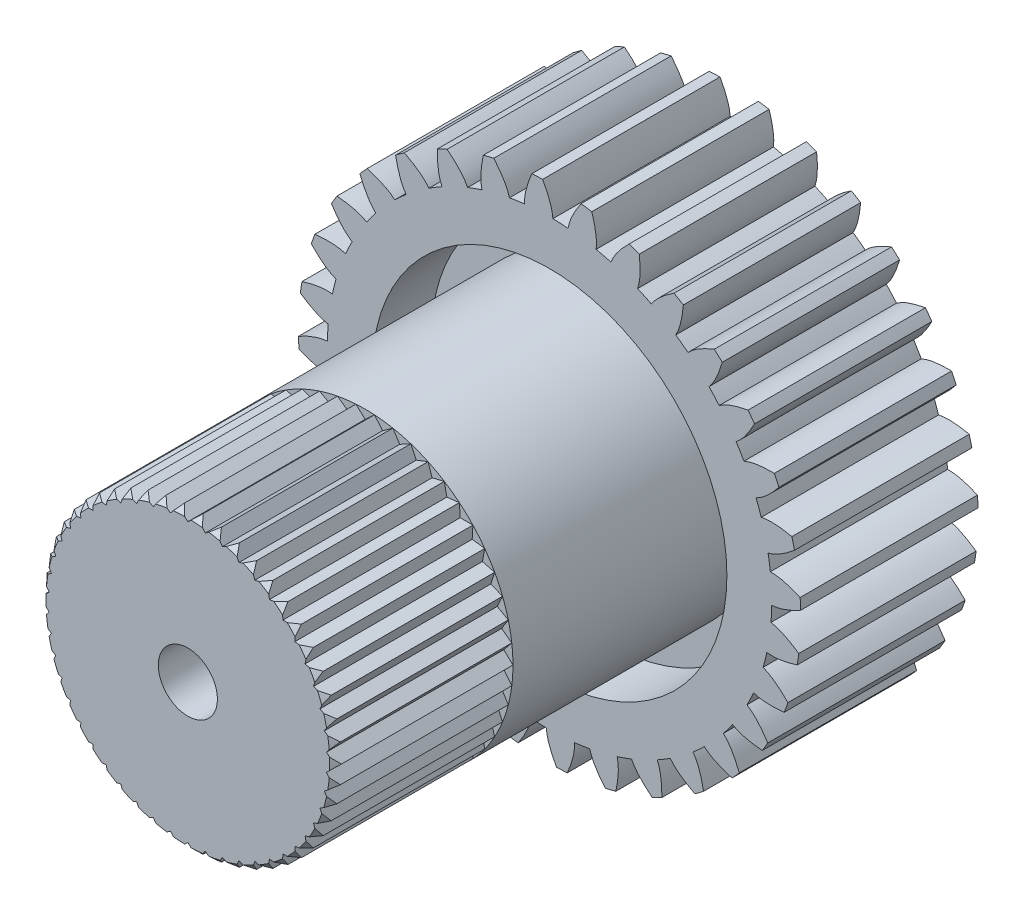
SolidWorks part; units mm, degrees
ref_plane "Front Plane" through (0, 0, 0) normal (0, 0, 1) x (1, 0, 0)
ref_plane "Top Plane" through (0, 0, 0) normal (0, 1, 0) x (1, 0, 0)
ref_plane "Right Plane" through (0, 0, 0) normal (1, 0, 0) x (0, 0, -1)
sketch "punti involuta" plane through (0, 0, 0) normal (0, 0, 1) x (1, 0, 0)
  line L0 (0, 0) -> (0, 4.6277) construction
  line L1 (-3.4916, 4) -> (3.4916, 4) construction
  line L2 (-3.4916, 2.7292) -> (3.4916, 5.2708) construction
  line L3 (0, 0) -> (-1.2856, 3.5321) construction
  line L4 (-1.2856, 3.5321) -> (0, 4) construction
  line L5 (-1.9173, 3.233) -> (-0.1385, 4.2879) construction
  line L6 (-0.9999, 3.6233) -> (0.0297, 3.9075) construction
  circle A0 centre (0, 0) radius 4 construction
  circle A1 centre (0, 0) radius 3.7588 construction
  arc A2 (-1.2856, 3.5321) -> (-1.9173, 3.233) centre (0, 0) ccw construction
  arc A3 (-1.2856, 3.5321) -> (-0.9999, 3.6233) centre (0, 0) cw construction
  arc A4 (-1.2856, 3.5321) -> (0.056, 3.7584) centre (0, 0) cw construction
  point P4 (0, 4)
  point P7 (0, 4)
  dimension "D1" = 8
  dimension "D2" = 20
  dimension "D3" = 1.3681
  dimension "D5" = 2.0681
  dimension "D7" = 1.0681
  dimension "D4" = 0.7
  dimension "D6" = 0.3
  dimension "D8" = 1.3681
sketch "diametro testa" plane through (0, 0, 0) normal (0, 0, 1) x (1, 0, 0)
  circle A0 centre (0, 0) radius 4.25
  dimension "D1" = 8.5
sketch "profilo" plane through (0, 0, 0) normal (0, 0, 1) x (1, 0, 0)
  line L0 (0, 0) -> (-0.1844, 3.7542) construction
  line L1 (0, 0) -> (0, 4.6277) construction
  line L2 (-0.1844, 3.7542) -> (-0.2085, 4.2449)
  arc A1 (-0.2085, 4.2449) -> (-0.1168, 4.2484) centre (0, 0) cw
  circle A3 centre (0, 0) radius 4.25 construction
  arc A4 (0.056, 3.7584) -> (-0.1844, 3.7542) centre (0, 0) ccw
  arc A5 (0.056, 3.7584) -> (-1.2856, 3.5321) centre (0, 0) ccw construction
  circle A6 centre (0, 0) radius 3.7588 construction
  spline S0 degree 3 poles (-0.1385, 4.2879) (-0.0478, 4.1243) (0.0412, 3.9487) (0.056, 3.7584) knots 0 0 0 0 1 1 1 1
  dimension "D1" = 2.813
sketch "diametro base" plane through (0, 0, 0) normal (0, 0, 1) x (1, 0, 0)
  circle A0 centre (0, 0) radius 3.7588
extrude "Boss-Extrude7" add sketch "profilo" along normal blind 3 contours S0 A1 L2 A4 region at (-0.0968, 3.9689, 0)
ref_plane "Plane1" through (0, 0, 0) normal (0.9988, 0.0491, 0) x (-0.0491, 0.9988, 0)
mirror "Mirror1" about plane through (0, 0, 0) normal (0.9988, 0.0491, 0) of bodies 112
pattern_circular "CirPattern1" count 32 over 360 about axis through (0, 0, 3) along (0, 0, 1) of bodies 113
extrude "Boss-Extrude9" add sketch "diametro base" along normal up to surface (3 mm away)
sketch "mozzo" plane through (0, 0, 0) normal (0, 0, 1) x (1, 0, 0)
  circle A0 centre (0, 0) radius 0.5
  dimension "D1" = 1
extrude "Cut-Extrude1" cut sketch "mozzo" along normal up to surface (3 mm away) up to face at (0, 0, 3)
sketch "Sketch1" plane through (0, 0, 3) normal (0, 0, 1) x (1, 0, 0)
  circle A0 centre (0, 0) radius 3
  dimension "D1" = 6
extrude "Cut-Extrude2" cut sketch "Sketch1" against normal blind 1
sketch "Sketch2" plane through (0, 0, 2) normal (0, 0, 1) x (1, 0, 0)
  circle A0 centre (0, 0) radius 2.5
  circle A1 centre (0, 0) radius 0.5 construction
  circle A2 centre (0, 0) radius 0.5
  dimension "D1" = 5
extrude "Boss-Extrude10" add sketch "Sketch2" along normal blind 7.12
chamfer "Chamfer1" distance 0.1 angle 45 1 edges at (2.5, 0, 9.12)
sketch "Sketch3" plane through (0, 0, 9.12) normal (0, 0, 1) x (1, 0, 0)
  line L0 (0, 0) -> (0, 4.8407) construction
  line L1 (0, 0) -> (-0.3045, 4.8407) construction
  line L2 (0, 0) -> (0.3045, 4.8407) construction
  line L3 (0, 2.35) -> (-0.157, 2.4951)
  line L4 (0, 2.35) -> (0.157, 2.4951)
  circle A1 centre (0, 0) radius 2.35 construction
  circle A2 centre (0, 0) radius 2.5 construction
  circle A3 centre (0, 0) radius 2.5 construction
  circle A4 centre (0, 0) radius 2.5 construction
  arc A5 (-0.157, 2.4951) -> (0.157, 2.4951) centre (0, 0) cw
  dimension "D2" = 4.7
  dimension "D1" = 3.6
extrude "Cut-Extrude3" cut sketch "Sketch3" against normal blind 3
pattern_circular "CirPattern2" count 50 over 360 about axis through (0, 0, 9.12) along (0, 0, 1) of "Cut-Extrude3"
equation "\"n_imposto\"= 32"
equation "\"m\"= .25"
equation "\"d_imposto\"= \"n_imposto\" * \"m\""
equation "\"alpha\"= 20"
equation "\"a1\"= .7"
equation "\"a2\"= .3"
equation "\"s\"= 3"
equation "\"D1@punti involuta\"=\"d_imposto\""
equation "\"D2@punti involuta\" = \"alpha\""
equation "\"D4@punti involuta\" = \"a1\""
equation "\"D5@punti involuta\" = \"D3@punti involuta\" + \"a1\""
equation "\"D6@punti involuta\" = \"a2\""
equation "\"D7@punti involuta\" = \"D3@punti involuta\" - \"a2\""
equation "\"D1@diametro testa\"=\"d_imposto\" + \"m\" * 2"
equation "\"D8@punti involuta\"=\"D3@punti involuta\""
equation "\"D1@profilo\"=360 / \"n_imposto\" / 4"
equation "\"D1@Boss-Extrude7\"=\"s\""
equation "\"D1@CirPattern1\"= \"n_imposto\""
equation "\"d_mozzo\"= 1"
equation "\"D1@mozzo\"=\"d_mozzo\""
